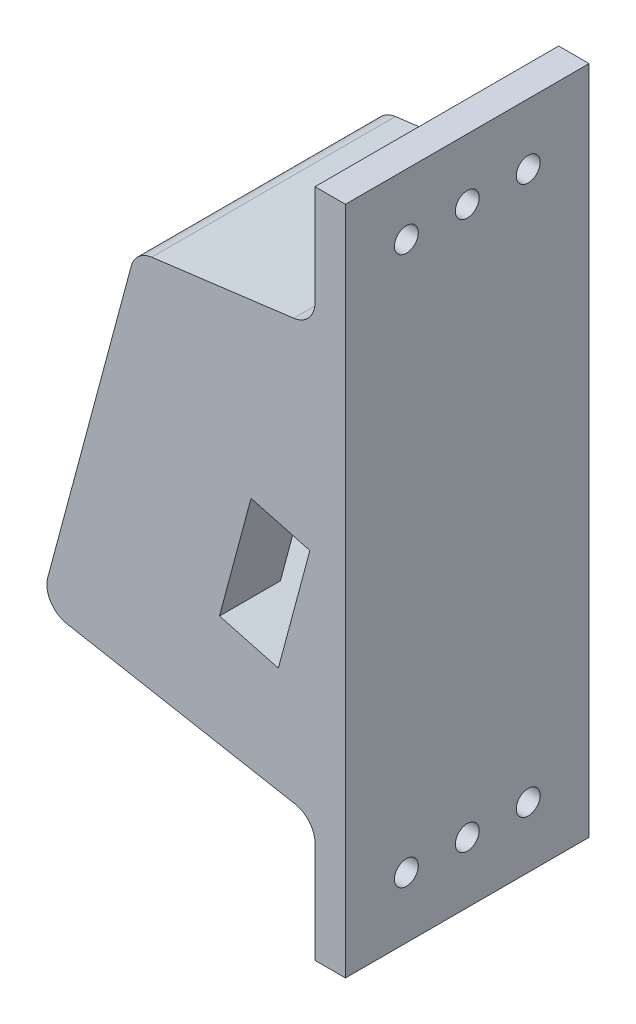
SolidWorks part; units mm, degrees
ref_plane "Front Plane" through (0, 0, 0) normal (0, 0, 1) x (1, 0, 0)
ref_plane "Top Plane" through (0, 0, 0) normal (0, 1, 0) x (1, 0, 0)
ref_plane "Right Plane" through (0, 0, 0) normal (1, 0, 0) x (0, 0, -1)
sketch "Sketch1" plane through (0, 0, 0) normal (0, 0, 1) x (1, 0, 0)
  line L10 (0, 0) -> (0, -139.7)
  line L16 (0, -139.7) -> (-6.35, -139.7)
  line L17 (-6.35, -139.7) -> (-6.35, -114.3)
  line L24 (-43.778, -30.1842) -> (-63.5, -103.7878)
  line L27 (0, 0) -> (-6.35, 0)
  line L28 (-6.35, 0) -> (-6.35, -25.4)
  line L30 (-6.35, -25.4) -> (-43.778, -30.1842)
  line L31 (-6.35, -114.3) -> (-63.5, -103.7878)
  point P0 (-63.5, -103.5594)
  point P3 (0, 0)
  point P7 (0, 0)
  point P8 (0, 0)
  point P10 (0, 0)
  point P11 (0, 0)
  point P12 (0, 0)
  dimension "D3" = 63.5
  dimension "D1" = 6.35
  dimension "D2" = 25.4
  dimension "D4" = 139.7
  dimension "D5" = 76.2
  dimension "D6" = 15
extrude "Boss-Extrude1" add sketch "Sketch1" along normal blind 50.8 contours L16 L17 L31 L24 L30 L28 L27 L10
sketch "Sketch3" plane through (-33.2994, 8.9225, 0) normal (-0.9659, 0.2588, 0) x (0, 0, 1)
  line L0 (25.4, -40.4863) -> (25.4, -70.1052) construction
  line L1 (3.175, -103.9863) -> (47.625, -103.9863)
  line L2 (3.175, -103.9863) -> (3.175, -53.1863)
  line L3 (3.175, -53.1863) -> (47.625, -53.1863)
  line L4 (47.625, -103.9863) -> (47.625, -53.1863)
  line L5 (3.175, -103.9863) -> (47.625, -53.1863) construction
  line L6 (3.175, -53.1863) -> (47.625, -103.9863) construction
  line L7 (50.8, -40.4863) -> (0, -40.4863) construction
  line L9 (50.8, -116.6863) -> (0, -116.6863) construction
  line L11 (6.4, -97.5863) -> (44.4, -97.5863) construction
  line L12 (6.4, -97.5863) -> (6.4, -59.5863) construction
  line L13 (6.4, -59.5863) -> (44.4, -59.5863) construction
  line L14 (44.4, -97.5863) -> (44.4, -59.5863) construction
  line L15 (6.4, -97.5863) -> (44.4, -59.5863) construction
  line L16 (6.4, -59.5863) -> (44.4, -97.5863) construction
  point P0 (25.4, -78.5863)
  point P10 (25.4, -78.5863)
  dimension "D4" = 38
  dimension "D1" = 44.45
  dimension "D2" = 50.8
  dimension "D3" = 12.7
extrude "Cut-Extrude1" cut sketch "Sketch3" against normal blind 25.4
sketch "Sketch4" plane through (-33.2994, 8.9225, 0) normal (-0.9659, 0.2588, 0) x (0, 0, 1)
  line L0 (3.175, -53.1863) -> (47.625, -53.1863) construction
  line L1 (3.175, -103.9863) -> (47.625, -103.9863) construction
  circle A2 centre (25.4, -46.8363) radius 2.4892
  circle A3 centre (25.4, -110.3363) radius 2.4892
  dimension "D1" = 4.9784
  dimension "D2" = 6.35
  dimension "D3" = 6.35
extrude "Cut-Extrude2" cut sketch "Sketch4" against normal blind 17.78 contours A2 | A3
sketch "Sketch7" plane through (-8.7648, 2.3485, 0) normal (-0.9659, 0.2588, 0) x (0, 0, 1)
  line L0 (47.625, -53.1863) -> (3.175, -103.9863) construction
  line L1 (12.7, -91.2863) -> (38.1, -91.2863)
  line L2 (12.7, -91.2863) -> (12.7, -65.8863)
  line L3 (12.7, -65.8863) -> (38.1, -65.8863)
  line L4 (38.1, -91.2863) -> (38.1, -65.8863)
  line L5 (12.7, -91.2863) -> (38.1, -65.8863) construction
  line L6 (12.7, -65.8863) -> (38.1, -91.2863) construction
  line L7 (3.175, -53.1863) -> (47.625, -103.9863) construction
  point P0 (25.4, -78.5863)
  point P14 (25.4, -78.5863)
  dimension "D1" = 25.4
  dimension "D2" = 25.4
extrude "Cut-Extrude3" cut sketch "Sketch7" against normal blind 19.05
sketch "Sketch9" plane through (0, 0, 38.1) normal (0, 0, -1) x (-1, 0, 0)
  line L0 (7.4166, -66.2233) -> (13.9906, -90.7578)
  line L5 (7.4166, -66.2233) -> (19.6838, -62.9363)
  line L6 (13.9906, -90.7578) -> (26.2579, -87.4708)
  line L7 (19.6838, -62.9363) -> (26.2579, -87.4708)
  dimension "D1" = 12.7
extrude "Cut-Extrude4" cut sketch "Sketch9" against normal through all and the other way through all
sketch "Sketch10" plane through (-6.35, 0, 0) normal (-1, 0, 0) x (0, 0, 1)
  line L0 (50.8, 0) -> (0, 0) construction
  line L1 (50.8, -139.7) -> (0, -139.7) construction
  line L2 (25.4, 0) -> (25.4, -25.4) construction
  line L3 (50.8, -25.4) -> (0, -25.4) construction
  circle A0 centre (25.4, -12.7) radius 2.4892
  circle A1 centre (12.7, -12.7) radius 2.4892
  circle A2 centre (12.7, -127) radius 2.4892
  circle A3 centre (38.1, -127) radius 2.4892
  circle A4 centre (38.1, -12.7) radius 2.4892
  circle A5 centre (25.4, -127) radius 2.4892
  dimension "D1" = 4.9784
  dimension "D2" = 12.7
  dimension "D3" = 12.7
  dimension "D4" = 12.7
  dimension "D5" = 12.7
extrude "Cut-Extrude5" cut sketch "Sketch10" against normal through all
fillet "Fillet1" radius 5.08 4 edges at (-63.5, -103.7878, 25.4) (-6.35, -114.3, 25.4) (-43.778, -30.1842, 25.4) (-6.35, -25.4, 25.4)
